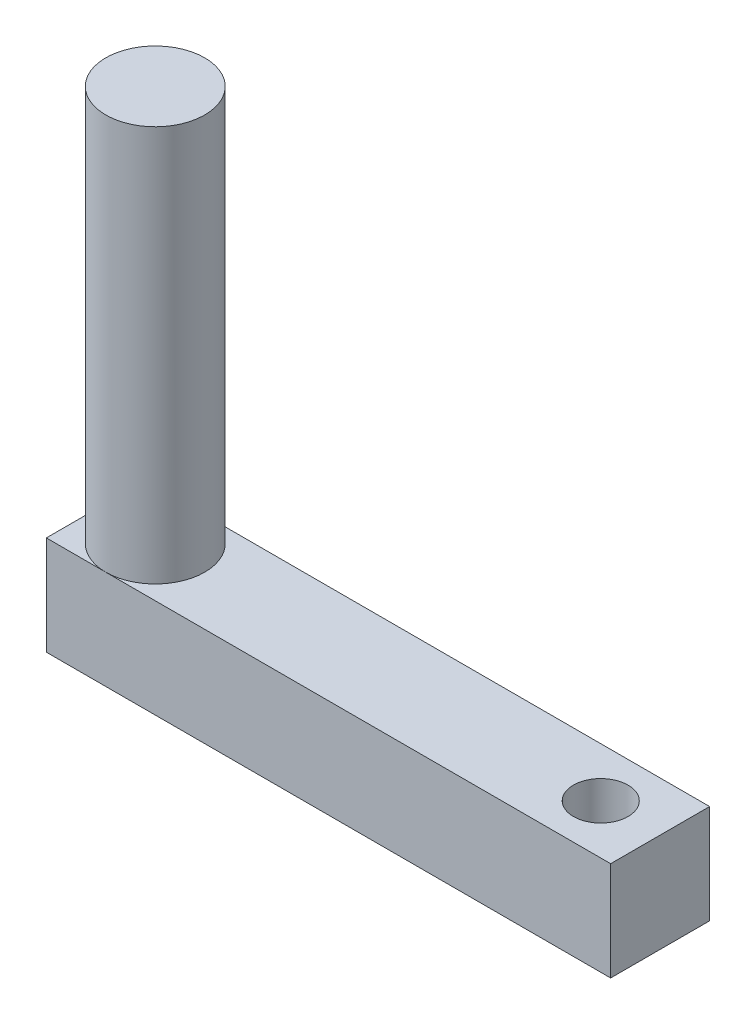
SolidWorks part; units mm, degrees
ref_plane "Front Plane" through (0, 0, 0) normal (0, 0, 1) x (1, 0, 0)
ref_plane "Top Plane" through (0, 0, 0) normal (0, 1, 0) x (1, 0, 0)
ref_plane "Right Plane" through (0, 0, 0) normal (1, 0, 0) x (0, 0, -1)
sketch "Sketch1" plane through (0, 0, 0) normal (0, 1, 0) x (1, 0, 0)
  line L1 (0, 0) -> (36.195, 0)
  line L2 (0, 0) -> (0, 6.35)
  line L3 (0, 6.35) -> (36.195, 6.35)
  line L4 (36.195, 0) -> (36.195, 6.35)
  circle A0 centre (3.81, 3.175) radius 1.75 construction
  circle A1 centre (32.385, 3.175) radius 1.75
  dimension "D1" = 3.5
  dimension "D2" = 28.575
  dimension "D3" = 3.81
  dimension "D4" = 3.81
  dimension "D5" = 6.35
  dimension "D6" = 3.175
extrude "Boss-Extrude1" add sketch "Sketch1" against normal blind 6.35
sketch "Sketch2" plane through (0, -6.35, 0) normal (0, -1, 0) x (1, 0, 0)
  line L1 (0, 0) -> (36.195, 0) construction
  circle A0 centre (3.81, -3.175) radius 3.175
  circle A1 centre (3.81, -3.175) radius 1.75 construction
  circle A2 centre (3.81, -3.175) radius 1.75 construction
extrude "Boss-Extrude2" add sketch "Sketch2" against normal blind 25.4 from offset 6.35 offset against normal yes
